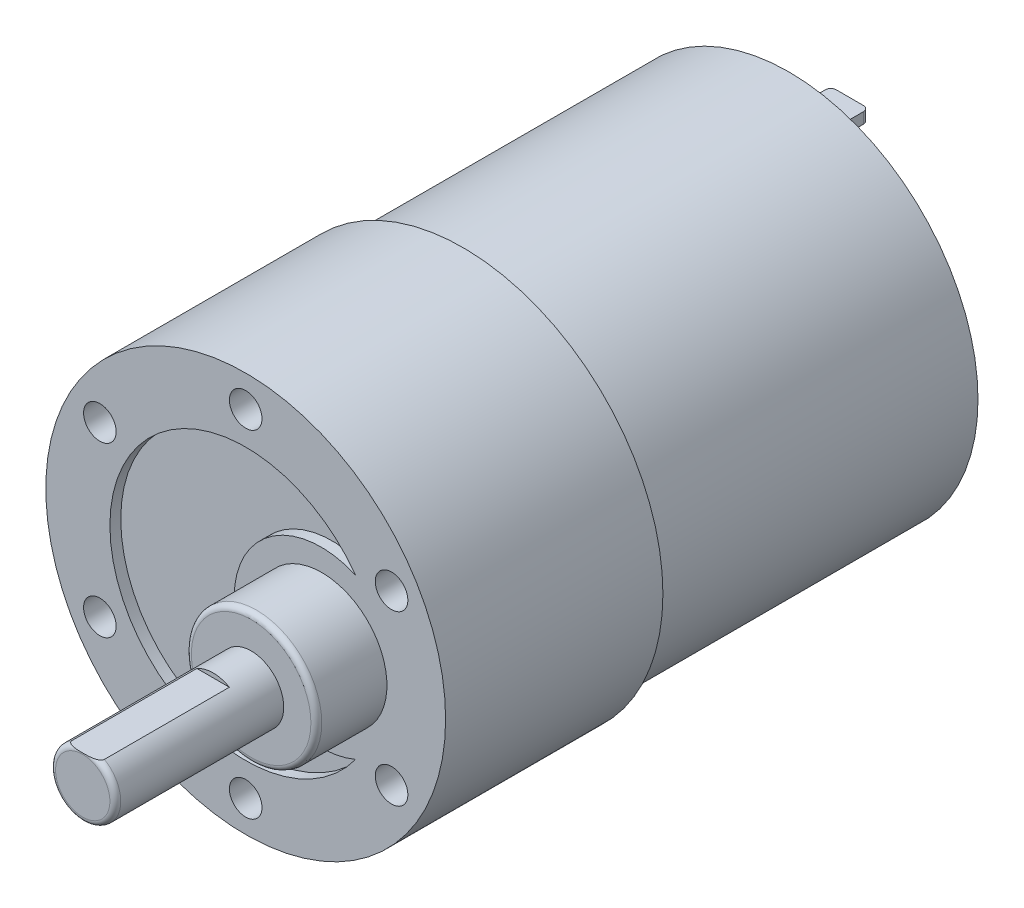
SolidWorks part; units mm, degrees
ref_plane "Front Plane" through (0, 0, 0) normal (0, 0, 1) x (1, 0, 0)
ref_plane "Top Plane" through (0, 0, 0) normal (0, 1, 0) x (1, 0, 0)
ref_plane "Right Plane" through (0, 0, 0) normal (1, 0, 0) x (0, 0, -1)
sketch "Sketch1" plane through (0, 0, 0) normal (0, 0, 1) x (1, 0, 0)
  circle A0 centre (0, 0) radius 18.4
  dimension "D1" = 36.8
extrude "Boss-Extrude1" add sketch "Sketch1" along normal blind 20
sketch "Sketch2" plane through (0, 0, 0) normal (0, 0, -1) x (-1, 0, 0)
  circle A0 centre (0, 0) radius 17.4
  dimension "D1" = 34.8
extrude "Boss-Extrude2" add sketch "Sketch2" along normal blind 30
sketch "Sketch3" plane through (0, 0, 20) normal (0, 0, 1) x (1, 0, 0)
  circle A0 centre (7, 0) radius 6
  dimension "D1" = 12
  dimension "D2" = 7
extrude "Boss-Extrude3" add sketch "Sketch3" along normal blind 6.5
fillet "Fillet1" radius 0.5 1 edges at (13, 0, 26.5)
sketch "Sketch4" plane through (0, 0, 26.5) normal (0, 0, 1) x (1, 0, 0)
  line L0 (7, -6.8172) -> (7, 7.1125) construction
  circle A0 centre (7, 0) radius 3
  dimension "D1" = 6
extrude "Boss-Extrude4" add sketch "Sketch4" along normal blind 15.5
sketch "Sketch5" plane through (0, 0, 42) normal (0, 0, 1) x (1, 0, 0)
  line L0 (5.5033, 2.6) -> (8.4967, 2.6)
  line L1 (7, -3) -> (9.3109, -3) construction
  circle A0 centre (7, 0) radius 3 construction
  circle A1 centre (7, 0) radius 3 construction
  arc A2 (8.4967, 2.6) -> (5.5033, 2.6) centre (7, 0) ccw
  dimension "D1" = 5.6
extrude "Cut-Extrude1" cut sketch "Sketch5" against normal blind 12
hole_wizard "Ø3.0 (3) Diameter Hole1" positions "Sketch7" profile "Sketch6" hole size "Ø3.0" standard "Ansi Metric"
sketch "Sketch7" plane through (0, 0, 20) normal (0, 0, 1) x (1, 0, 0)
  point P0 (-13.4234, 7.75)
  point P1 (-13.4234, -7.75)
  point P3 (0, -15.5)
  point P5 (13.4234, 7.75)
  point P7 (0, 15.5)
  point P22 (13.4234, -7.75)
  dimension "D1" = 15.5
  dimension "D2" = 15.5
  dimension "D3" = 15.5
  dimension "D4" = 15.5
  dimension "D5" = 15.5
  dimension "D6" = 15.5
  dimension "D7" = 15.5
  dimension "D8" = 15.5
  dimension "D9" = 15.5
  dimension "D10" = 15.5
sketch "Sketch6" plane through (-13.4234, 7.75, 20) normal (1, 0, 0) x (0, -1, 0)
  line L0 (0, 0) -> (0, 3.9013)
  line L1 (0, 3.9013) -> (1.5, 3)
  line L2 (1.5, 3) -> (1.5, 0)
  line L5 (1.5, 0) -> (0, 0)
  line L10 (0, 3.9013) -> (-1.5, 3) construction
  line L11 (0, -6.35) -> (0, 107.95) construction
  dimension "Hole Dia." = 3
  dimension "Hole Depth" = 3
  dimension "Drill Angle" = 118
sketch "Sketch8" plane through (0, 0, 20) normal (0, 0, 1) x (1, 0, 0)
  line L0 (-0.5907, 0) -> (14.4711, 0) construction
  line L1 (7, 7.3586) -> (7, -7.457) construction
  arc A0 (10.1162, 7.3426) -> (10.1162, -7.3426) centre (0, 0) ccw
  arc A1 (10.1162, 7.3426) -> (10.1162, -7.3426) centre (6.9402, 0) ccw
  dimension "D1" = 25
  dimension "D2" = 16
extrude "Cut-Extrude2" cut sketch "Sketch8" against normal blind 1
sketch "Sketch9" plane through (0, 0, -30) normal (0, 0, -1) x (-1, 0, 0)
  circle A0 centre (0, 0) radius 4
  dimension "D1" = 8
extrude "Boss-Extrude5" add sketch "Sketch9" along normal blind 1
fillet "Fillet2" radius 0.5 1 edges at (-4, 0, -31)
ref_plane "Plane1" through (0, 0, -33) normal (0, 0, -1) x (-1, 0, 0)
sketch "Sketch10" plane through (0, 0, -33) normal (0, 0, -1) x (-1, 0, 0)
  circle A0 centre (0, 0) radius 14
  dimension "D1" = 28
extrude "Boss-Extrude6" [suppressed] add sketch "Sketch10" along normal blind 1.5 separate body
sketch "Sketch11" plane through (0, 0, -30) normal (0, 0, -1) x (-1, 0, 0)
  line L0 (0, 11.55) -> (0, 12.55) construction
  line L1 (-1.75, 12.55) -> (1.75, 12.55)
  line L2 (-1.75, 12.55) -> (-1.75, 11.55)
  line L3 (-1.75, 11.55) -> (1.75, 11.55)
  line L4 (1.75, 12.55) -> (1.75, 11.55)
  line L5 (-1.75, 12.05) -> (1.75, 12.05) construction
  line L6 (-3.5, 0) -> (3.5, 0) construction
  line L7 (1.75, -12.55) -> (1.75, -11.55)
  line L8 (-1.75, -12.55) -> (-1.75, -11.55)
  line L9 (-1.75, -12.55) -> (1.75, -12.55)
  line L10 (-1.75, -11.55) -> (1.75, -11.55)
  circle A0 centre (0, 0) radius 3.5 construction
  dimension "D1" = 3.5
  dimension "D2" = 1
  dimension "D3" = 12.05
extrude "Boss-Extrude7" add sketch "Sketch11" along normal blind 5.6
fillet "Fillet3" radius 0.5 4 edges at (-1.75, -12.05, -35.6) (1.75, -12.05, -35.6) (-1.75, 12.05, -35.6) (1.75, 12.05, -35.6)
ref_plane "Plane2" [suppressed] through (0, 0, -36.5) normal (0, 0, -1) x (-1, 0, 0)
sketch "Sketch13" [suppressed] plane through (0, 0, -36.5) normal (0, 0, -1) x (-1, 0, 0)
  circle A0 centre (0, 0) radius 9
  dimension "D1" = 18
extrude "Boss-Extrude8" [suppressed] add sketch "Sketch13" along normal blind 3 separate body
sketch "Sketch14" plane through (0, 0, -31) normal (0, 0, -1) x (-1, 0, 0)
  circle A0 centre (0, 0) radius 1.5
  dimension "D1" = 3
extrude "Boss-Extrude9" add sketch "Sketch14" along normal blind 8.55
fillet "Fillet4" radius 0.5 1 edges at (7, -3, 42)
